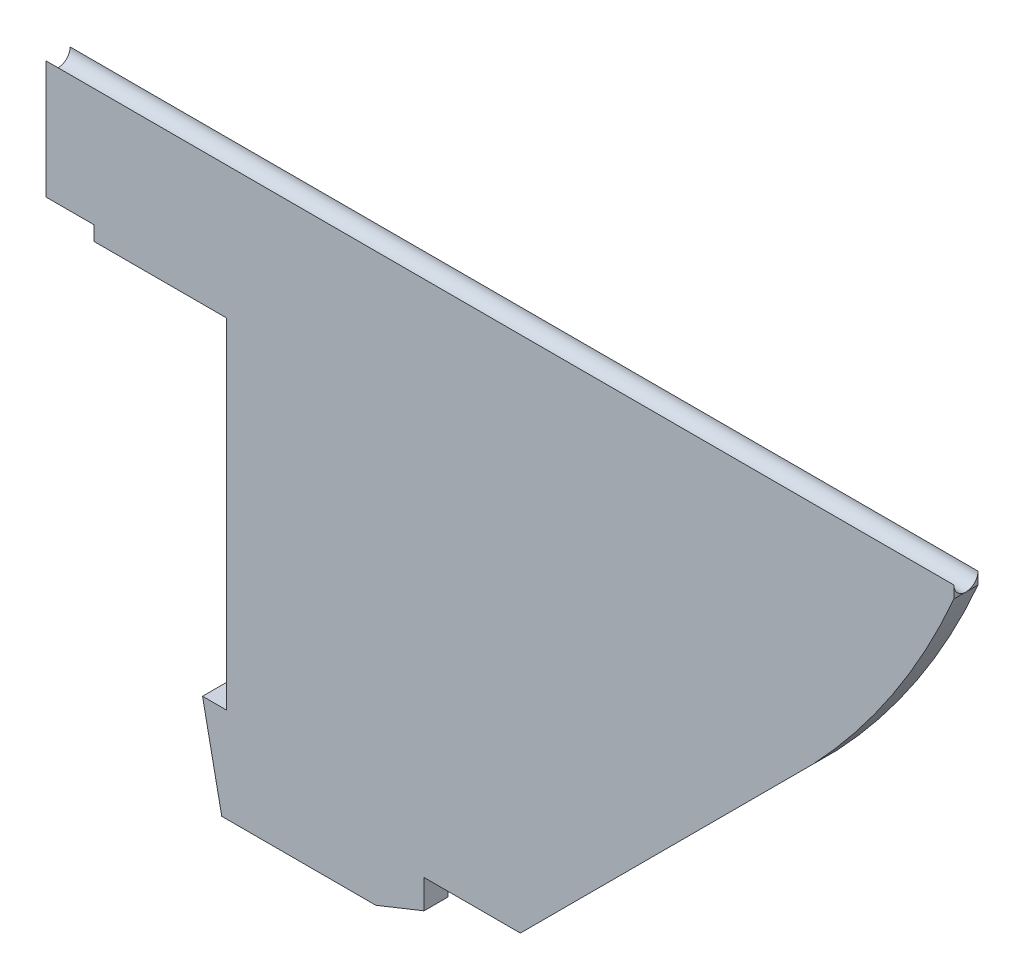
SolidWorks part; units mm, degrees
material "Papier ondulé"
ref_plane "Plan de face" through (0, 0, 0) normal (0, 0, 1) x (1, 0, 0)
ref_plane "Plan de dessus" through (0, 0, 0) normal (0, 1, 0) x (1, 0, 0)
ref_plane "Plan de droite" through (0, 0, 0) normal (1, 0, 0) x (0, 0, -1)
sketch "Esquisse1" plane through (0, 0, 0) normal (0, 0, 1) x (1, 0, 0)
  line L0 (0, 0) -> (188.5, 0) construction
  line L1 (0, 0) -> (0, -25)
  line L2 (0, -25) -> (37.5, -25)
  line L3 (37.5, -25) -> (37.5, -95.5)
  line L4 (37.5, -95.5) -> (32.5, -95.5)
  line L5 (32.5, -95.5) -> (36.4874, -115.0985)
  line L6 (36.4874, -115.0985) -> (88.4874, -115.0985)
  line L7 (88.4874, -115.0985) -> (159.198, -44.3878)
  line L8 (43.6829, 43.9989) -> (200.1829, 45.1267)
  arc A0 (0, 0) -> (43.6829, 43.9989) centre (44, 0) cw
  arc A1 (159.198, -44.3878) -> (200.1829, 45.1267) centre (49.0805, 60.1702) ccw
  dimension "D11" = 44
  dimension "D1" = 188.5
  dimension "D2" = 25
  dimension "D3" = 37.5
  dimension "D4" = 90
  dimension "D5" = 70.5
  dimension "D6" = 5
  dimension "D7" = 20
  dimension "D8" = 52
  dimension "D9" = 135
  dimension "D10" = 100
  dimension "D12" = 156.5
extrude "Boss.-Extru.1" add sketch "Esquisse1" along normal blind 5
sketch "Esquisse2" plane through (0, 0, 5) normal (0, 0, 1) x (1, 0, 0)
  line L0 (0, 0) -> (188.5, 0)
  line L2 (0, 0) -> (-15.6326, 12.4435)
  line L3 (-15.6326, 12.4435) -> (19.4776, 66.0889)
  line L4 (19.4776, 66.0889) -> (219.452, 63.38)
  line L5 (219.452, 63.38) -> (209.3622, -2.4607)
  line L6 (209.3622, -2.4607) -> (188.5, 0)
  dimension "D1" = 188.5
sketch "Esquisse3" plane through (0, 0, 5) normal (0, 0, 1) x (1, 0, 0)
  line L1 (0, -25) -> (10, -25)
  line L2 (0, -25) -> (0, -22)
  line L3 (0, -22) -> (10, -22)
  line L4 (10, -25) -> (10, -22)
  dimension "D1" = 10
  dimension "D2" = 3
extrude "Enlèv. mat.-Extru.1" cut sketch "Esquisse3" against normal through all
sketch "Esquisse4" plane through (0, 0, 5) normal (0, 0, 1) x (1, 0, 0)
  line L0 (88.4874, -115.0985) -> (88.4874, -105.0985) construction
  line L1 (88.4874, -105.0985) -> (78.4874, -105.0985)
  line L2 (78.4874, -105.0985) -> (78.4874, -115.0985) construction
  line L3 (36.4874, -115.0985) -> (88.4874, -115.0985) construction
  line L4 (78.4874, -115.0985) -> (88.4874, -115.0985)
  line L5 (88.4874, -105.0985) -> (98.4874, -105.0985)
  line L6 (88.4874, -115.0985) -> (159.198, -44.3878) construction
  line L7 (98.4874, -105.0985) -> (88.4874, -115.0985)
  line L8 (78.4874, -105.0985) -> (78.4874, -111.0985)
  line L9 (78.4874, -111.0985) -> (68.4874, -115.0985)
  line L10 (68.4874, -115.0985) -> (78.4874, -115.0985)
  dimension "D1" = 10
  dimension "D2" = 10
  dimension "D3" = 10
  dimension "D4" = 4
extrude "Enlèv. mat.-Extru.2" cut sketch "Esquisse4" against normal through all
extrude "Enlèv. mat.-Extru.3" cut sketch "Esquisse2" against normal through all
sketch "Esquisse5" plane through (0, 0, 0) normal (-1, 0, 0) x (0, 0, 1)
  line L0 (5, 0) -> (5, 2.5)
  line L1 (5, 0) -> (2.5, 0)
  line L2 (5, 0) -> (0, 0) construction
  line L3 (2.5, 0) -> (0, 0)
  line L4 (0, 0) -> (0, 2.5)
  arc A0 (0, 2.5) -> (5, 2.5) centre (2.5, 2.5) ccw
  dimension "D1" = 2.5
extrude "Boss.-Extru.2" add sketch "Esquisse5" along direction (1, 0, 0) on the side against the normal up to vertex (188.5 mm away) contours A0 L0 | A0 L4 region at (0, 0.5584, 4.4416) region at (0, 0.5584, 0.5584) up to point (188.5, 0, 0)
